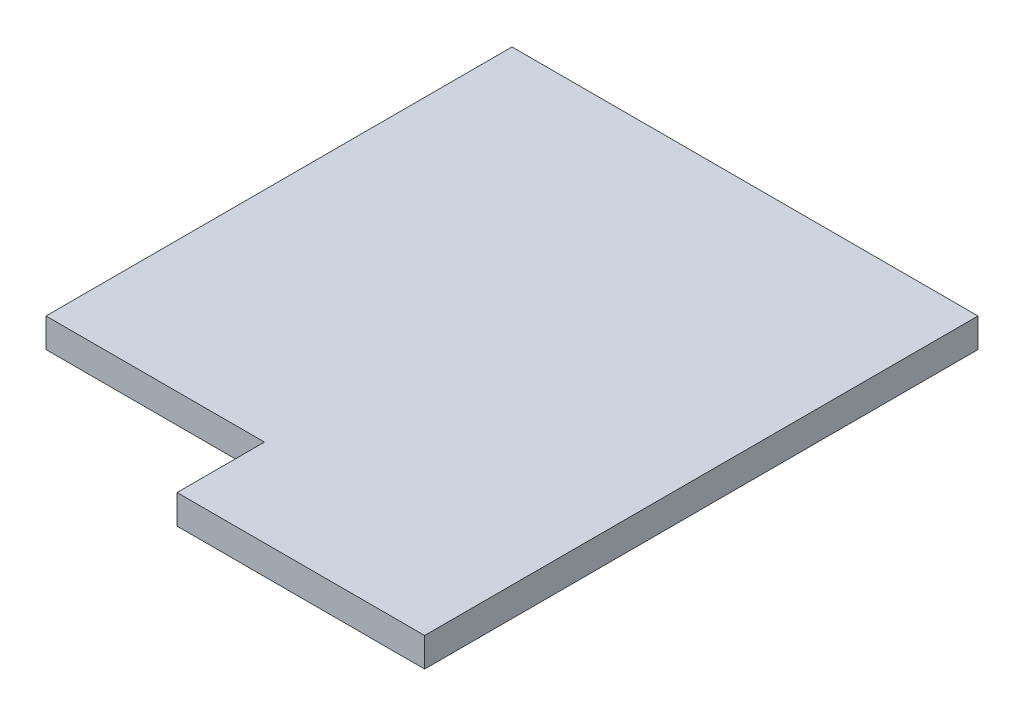
SolidWorks part; units mm, degrees
ref_plane "Front Plane" through (0, 0, 0) normal (0, 0, 1) x (1, 0, 0)
ref_plane "Top Plane" through (0, 0, 0) normal (0, 1, 0) x (1, 0, 0)
ref_plane "Right Plane" through (0, 0, 0) normal (1, 0, 0) x (0, 0, -1)
sketch "Sketch1" plane through (0, 0, 0) normal (0, 1, 0) x (1, 0, 0)
  line L0 (-25.4, -25.4) -> (-1.5875, -25.4)
  line L1 (-25.4, 25.4) -> (25.4, 25.4)
  line L2 (-25.4, 25.4) -> (-25.4, -25.4)
  line L4 (25.4, 25.4) -> (25.4, -25.4)
  line L5 (-25.4, 25.4) -> (25.4, -25.4) construction
  line L6 (-25.4, -25.4) -> (25.4, 25.4) construction
  line L8 (-1.5875, -25.4) -> (-1.5875, -34.925)
  line L9 (-1.5875, -34.925) -> (25.4, -34.925)
  line L10 (25.4, -34.925) -> (25.4, -25.4)
  point P0 (0, 0)
  point P6 (-1.089, -34.925)
  dimension "D1" = 50.8
  dimension "D2" = 26.9875
extrude "Boss-Extrude1" add sketch "Sketch1" along normal blind 3.175
